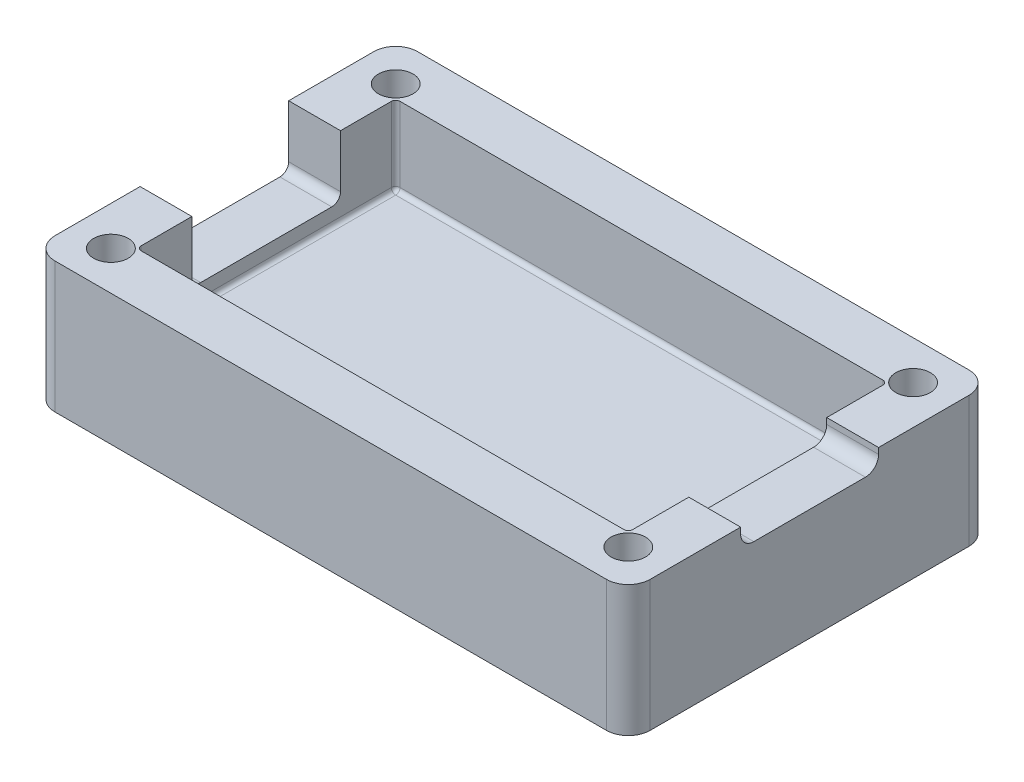
SolidWorks part; units mm, degrees
ref_plane "Front Plane" through (0, 0, 0) normal (0, 0, 1) x (1, 0, 0)
ref_plane "Top Plane" through (0, 0, 0) normal (0, 1, 0) x (1, 0, 0)
ref_plane "Right Plane" through (0, 0, 0) normal (1, 0, 0) x (0, 0, -1)
sketch "Sketch1" plane through (0, 0, 0) normal (0, 1, 0) x (1, 0, 0)
  line L0 (59.9293, 4.4568) -> (59.9293, -13.9892) construction
  line L1 (59.9293, 5.7268) -> (25.4813, 5.7268)
  line L2 (59.9293, 5.7268) -> (59.9293, -15.2592)
  line L3 (59.9293, -15.2592) -> (25.4813, -15.2592)
  line L4 (25.4813, 5.7268) -> (25.4813, -15.2592)
  line L5 (59.9293, 5.7268) -> (25.4813, -15.2592) construction
  line L6 (59.9293, -15.2592) -> (25.4813, 5.7268) construction
  line L7 (26.7513, 5.7268) -> (58.6593, 5.7268) construction
  line L8 (25.4813, -13.9892) -> (25.4813, 4.4568) construction
  line L9 (58.6593, -15.2592) -> (26.7513, -15.2592) construction
  point P0 (0, 0)
extrude "Boss-Extrude1" add sketch "Sketch1" along normal blind 7.572
sketch "Sketch3" plane through (0, 7.572, 0) normal (0, 1, 0) x (1, 0, 0)
  line L1 (56.9293, -12.2592) -> (28.4813, -12.2592)
  line L2 (56.9293, -12.2592) -> (56.9293, 2.7268)
  line L3 (56.9293, 2.7268) -> (28.4813, 2.7268)
  line L4 (28.4813, -12.2592) -> (28.4813, 2.7268)
  line L5 (56.9293, -12.2592) -> (28.4813, 2.7268) construction
  line L6 (56.9293, 2.7268) -> (28.4813, -12.2592) construction
  line L8 (56.9293, 2.4728) -> (56.9293, -0.7748) construction
  line L9 (28.7353, 2.7268) -> (56.6753, 2.7268) construction
  line L10 (56.6753, -12.2592) -> (28.7353, -12.2592) construction
  line L11 (28.4813, -12.0052) -> (28.4813, -9.0657) construction
  point P0 (0, 0)
extrude "Cut-Extrude1" cut sketch "Sketch3" against normal blind 4.572
fillet "Fillet1" radius 1.27 4 edges at (25.4813, 3.786, -5.7268) (59.9293, 3.786, -5.7268) (25.4813, 3.786, 15.2592) (59.9293, 3.786, 15.2592)
fillet "Fillet2" radius 0.254 4 edges at (56.9293, 5.286, -2.7268) (56.9293, 5.286, 12.2592) (28.4813, 5.286, 12.2592) (28.4813, 5.286, -2.7268)
fillet "Fillet3" radius 0.254 8 edges at (56.8549, 3, 12.1848) (42.7053, 3, 12.2592) (28.5557, 3, 12.1848) (28.4813, 3, 4.7662) (28.5557, 3, -2.6524) (42.7053, 3, -2.7268) (56.8549, 3, -2.6524) (56.9293, 3, 4.7662)
sketch "Sketch5" plane through (25.4813, 0, 0) normal (-1, 0, 0) x (0, 0, 1)
  line L0 (-4.4568, 7.572) -> (13.9892, 7.572) construction
  line L1 (9.0657, 7.572) -> (0.4666, 7.572)
  line L2 (9.0657, 7.572) -> (9.0657, 4.0064)
  line L3 (9.0657, 4.0064) -> (0.4666, 4.0064)
  line L4 (0.4666, 7.572) -> (0.4666, 4.0064)
  line L5 (-4.4568, 0) -> (13.9892, 0) construction
  line L6 (0.4666, 9.5831) -> (0.4666, 7.572) construction
  point P8 (4.7662, 7.572)
  point P9 (4.7662, 0)
extrude "Cut-Extrude3" cut sketch "Sketch5" against normal up to surface (3 mm away) up to face at (28.4813, 5.413, 4.7662)
fillet "Fillet4" radius 0.508 2 edges at (26.9813, 4.0064, 0.4666) (26.9813, 4.0064, 9.0657)
ref_plane "Plane1" through (56.6753, 3, -2.4728) normal (0, 0, -1) x (-1, 0, 0)
sketch "Sketch7" plane through (59.9293, 0, 0) normal (1, 0, 0) x (0, 0, -1)
  line L0 (4.4568, 7.572) -> (-0.7748, 7.572) construction
  line L1 (-0.7748, 7.572) -> (-8.7576, 7.572)
  line L2 (-0.7748, 7.572) -> (-0.7748, 6.4638)
  line L3 (-0.7748, 6.4638) -> (-8.7576, 6.4638)
  line L4 (-8.7576, 7.572) -> (-8.7576, 6.4638)
  line L5 (-13.9892, 0) -> (4.4568, 0) construction
  point P6 (-4.7662, 6.4638)
  point P9 (-4.7662, 0)
extrude "Cut-Extrude4" cut sketch "Sketch7" against normal up to surface (3 mm away) up to face at (56.9293, 5.413, 4.7662)
fillet "Fillet5" radius 0.762 2 edges at (58.4293, 6.4638, 8.7576) (58.4293, 6.4638, 0.7748)
sketch "Sketch8" plane through (0, 0, 0) normal (0, -1, 0) x (-1, 0, 0)
  line L0 (-59.5573, -14.8872) -> (-56.8549, -12.1848) construction
  line L9 (-57.6774, -13.0073) -> (-27.7332, -13.0073) construction
  line L10 (-57.6774, -13.0073) -> (-57.6774, 3.4749) construction
  line L11 (-57.6774, 3.4749) -> (-27.7332, 3.4749) construction
  line L12 (-27.7332, -13.0073) -> (-27.7332, 3.4749) construction
  line L13 (-57.6774, -13.0073) -> (-27.7332, 3.4749) construction
  line L14 (-57.6774, 3.4749) -> (-27.7332, -13.0073) construction
  circle A0 centre (-57.6774, 3.4749) radius 2
  circle A1 centre (-27.7332, 3.4749) radius 2
  circle A2 centre (-27.7332, -13.0073) radius 2
  circle A3 centre (-57.6774, -13.0073) radius 2
  arc A6 (-59.9293, -13.9892) -> (-58.6593, -15.2592) centre (-58.6593, -13.9892) ccw construction
  point P0 (0, 0)
  dimension "D1" = 4
extrude "Cut-Extrude5" cut sketch "Sketch8" against normal blind 2
sketch "Sketch9" plane through (0, 0, 0) normal (0, -1, 0) x (-1, 0, 0)
  circle A0 centre (-57.6774, 3.4749) radius 1
  circle A2 centre (-27.7332, 3.4749) radius 1
  circle A3 centre (-27.7332, -13.0073) radius 1
  circle A4 centre (-57.6774, -13.0073) radius 1
  circle A8 centre (-57.6774, -13.0073) radius 2 construction
  circle A9 centre (-57.6774, 3.4749) radius 2 construction
  circle A10 centre (-27.7332, 3.4749) radius 2 construction
  circle A11 centre (-27.7332, -13.0073) radius 2 construction
  dimension "D1" = 2
extrude "Cut-Extrude7" cut sketch "Sketch9" against normal through all
